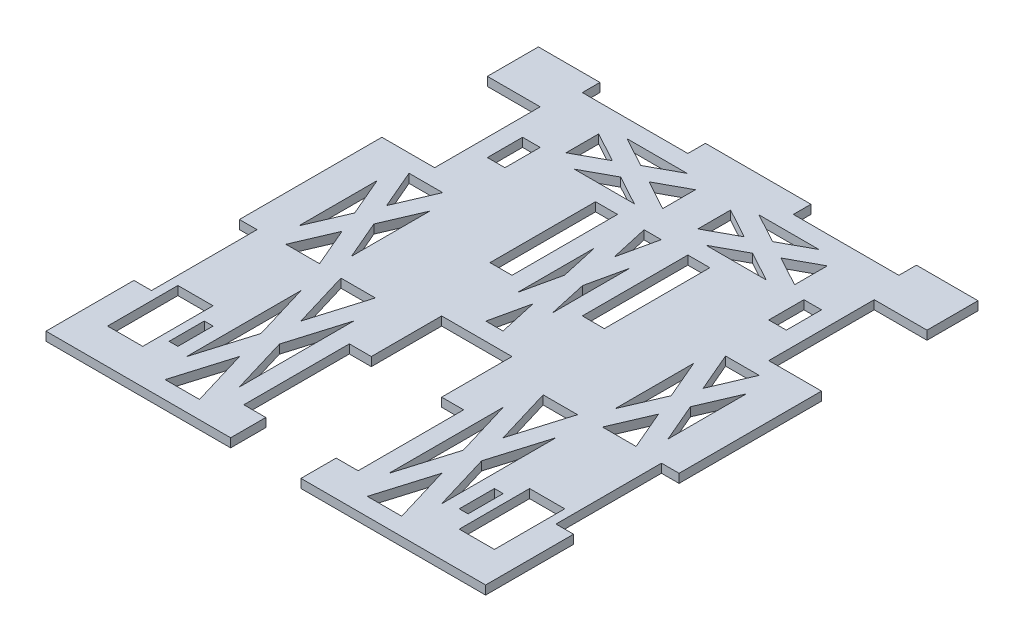
SolidWorks part; units mm, degrees
material "7050-T73510"
ref_plane "Front Plane" through (0, 0, 0) normal (0, 0, 1) x (1, 0, 0)
ref_plane "Top Plane" through (0, 0, 0) normal (0, 1, 0) x (1, 0, 0)
ref_plane "Right Plane" through (0, 0, 0) normal (1, 0, 0) x (0, 0, -1)
sketch "Sketch1" plane through (0, 0, 0) normal (0, 1, 0) x (1, 0, 0)
  line L1 (-158.75, -177.8) -> (158.75, -177.8)
  line L2 (-158.75, -177.8) -> (-158.75, 177.8)
  line L3 (-158.75, 177.8) -> (158.75, 177.8)
  line L4 (158.75, -177.8) -> (158.75, 177.8)
  line L5 (-158.75, -177.8) -> (158.75, 177.8) construction
  line L6 (-158.75, 177.8) -> (158.75, -177.8) construction
  point P0 (0, 0)
  dimension "D1" = 355.6
  dimension "D2" = 317.5
extrude "Boss-Extrude1" add sketch "Sketch1" along normal blind 6.35
sketch "Sketch2" plane through (0, 6.35, 0) normal (0, 1, 0) x (1, 0, 0)
  line L0 (-158.75, -177.8) -> (158.75, -177.8) construction
  line L1 (-25.4, -25.4) -> (25.4, -25.4)
  line L2 (-25.4, -25.4) -> (-25.4, -177.8)
  line L3 (-25.4, -177.8) -> (25.4, -177.8)
  line L4 (25.4, -25.4) -> (25.4, -177.8)
  line L5 (-25.4, -25.4) -> (25.4, -177.8) construction
  line L6 (-25.4, -177.8) -> (25.4, -25.4) construction
  point P0 (0, -101.6)
  dimension "D1" = 152.4
  dimension "D2" = 50.8
extrude "Cut-Extrude1" cut sketch "Sketch2" against normal through all
sketch "Sketch3" plane through (0, 6.35, 0) normal (0, 1, 0) x (1, 0, 0)
  line L0 (158.75, -177.8) -> (158.75, 177.8) construction
  line L5 (146.05, 140.97) -> (120.65, 140.97)
  line L11 (146.05, 140.97) -> (146.05, 64.77)
  line L13 (146.05, 64.77) -> (120.65, 64.77)
  line L15 (120.65, 140.97) -> (120.65, 64.77)
  line L16 (158.75, 177.8) -> (-158.75, 177.8) construction
  line L17 (107.95, 90.17) -> (95.25, 90.17)
  line L18 (107.95, 90.17) -> (107.95, 115.57)
  line L19 (107.95, 115.57) -> (95.25, 115.57)
  line L20 (95.25, 90.17) -> (95.25, 115.57)
  line L21 (0, -3.4925) -> (0, 3.4925) construction
  line L22 (-95.25, 90.17) -> (-95.25, 115.57)
  line L23 (-107.95, 115.57) -> (-95.25, 115.57)
  line L24 (-107.95, 90.17) -> (-107.95, 115.57)
  line L25 (-107.95, 90.17) -> (-95.25, 90.17)
  line L26 (-120.65, 140.97) -> (-120.65, 64.77)
  line L27 (-146.05, 64.77) -> (-120.65, 64.77)
  line L28 (-146.05, 140.97) -> (-146.05, 64.77)
  line L29 (-146.05, 140.97) -> (-120.65, 140.97)
  point P14 (107.95, 102.87)
  point P15 (120.65, 102.87)
  dimension "D1" = 25.4
  dimension "D2" = 12.7
  dimension "D3" = 12.7
  dimension "D4" = 12.7
  dimension "D5" = 25.4
  dimension "D6" = 76.2
  dimension "D7" = 36.83
extrude "Cut-Extrude2" cut sketch "Sketch3" against normal through all contours L5 L15 L13 L11 | L20 L17 L18 L19 | L29 L28 L27 L26 | L24 L25 L22 L23 | L26 L27 L28 L29 region at (133.35, 6.35, -102.87) region at (101.6, 6.35, -102.87) region at (-101.6, 6.35, -102.87) region at (-133.35, 6.35, -102.87)
sketch "Sketch4" plane through (0, 6.35, 0) normal (0, 1, 0) x (1, 0, 0)
  line L0 (-158.75, 177.8) -> (-158.75, -177.8) construction
  line L1 (-158.75, 140.97) -> (-146.05, 140.97)
  line L2 (-158.75, 140.97) -> (-158.75, 64.77)
  line L3 (-158.75, 64.77) -> (-146.05, 64.77)
  line L4 (-146.05, 140.97) -> (-146.05, 64.77)
  line L5 (0, -3.4925) -> (0, 3.4925) construction
  line L6 (-158.75, -114.3) -> (-146.05, -114.3)
  line L7 (-158.75, -114.3) -> (-158.75, -38.1)
  line L8 (-158.75, -38.1) -> (-146.05, -38.1)
  line L9 (-146.05, -114.3) -> (-146.05, -38.1)
  line L10 (158.75, 64.77) -> (146.05, 64.77)
  line L11 (146.05, 140.97) -> (146.05, 64.77)
  line L12 (158.75, 140.97) -> (146.05, 140.97)
  line L13 (158.75, 140.97) -> (158.75, 64.77)
  line L14 (158.75, -38.1) -> (146.05, -38.1)
  line L15 (146.05, -114.3) -> (146.05, -38.1)
  line L16 (158.75, -114.3) -> (146.05, -114.3)
  line L17 (158.75, -114.3) -> (158.75, -38.1)
  line L18 (158.75, 177.8) -> (-158.75, 177.8) construction
  line L19 (114.3, 165.1) -> (38.1, 165.1)
  line L20 (-114.3, 177.8) -> (-38.1, 177.8)
  line L21 (-114.3, 177.8) -> (-114.3, 165.1)
  line L22 (-114.3, 165.1) -> (-38.1, 165.1)
  line L23 (-38.1, 177.8) -> (-38.1, 165.1)
  line L24 (38.1, 177.8) -> (38.1, 165.1)
  line L25 (114.3, 177.8) -> (38.1, 177.8)
  line L26 (114.3, 177.8) -> (114.3, 165.1)
  line L27 (-25.4, -25.4) -> (-25.4, -177.8) construction
  line L28 (-25.4, -152.4) -> (-41.275, -152.4)
  line L29 (-25.4, -152.4) -> (-25.4, -76.2)
  line L30 (-25.4, -76.2) -> (-41.275, -76.2)
  line L31 (-41.275, -152.4) -> (-41.275, -76.2)
  line L32 (-158.75, -177.8) -> (-25.4, -177.8) construction
  line L33 (25.4, 101.6) -> (41.275, 101.6)
  line L34 (-25.4, 25.4) -> (-41.275, 25.4)
  line L35 (-25.4, 25.4) -> (-25.4, 101.6)
  line L36 (-25.4, 101.6) -> (-41.275, 101.6)
  line L37 (-41.275, 25.4) -> (-41.275, 101.6)
  line L38 (41.275, 25.4) -> (41.275, 101.6)
  line L39 (25.4, 25.4) -> (41.275, 25.4)
  line L40 (25.4, 25.4) -> (25.4, 101.6)
  line L41 (25.4, -76.2) -> (41.275, -76.2)
  line L42 (41.275, -152.4) -> (41.275, -76.2)
  line L43 (25.4, -152.4) -> (41.275, -152.4)
  line L44 (25.4, -152.4) -> (25.4, -76.2)
  dimension "D1" = 12.7
  dimension "D2" = 12.7
  dimension "D3" = 76.2
  dimension "D4" = 76.2
  dimension "D5" = 36.83
  dimension "D6" = 215.9
  dimension "D7" = 12.7
  dimension "D8" = 76.2
  dimension "D9" = 76.2
  dimension "D10" = 15.875
  dimension "D11" = 76.2
  dimension "D12" = 25.4
  dimension "D13" = 76.2
  dimension "D14" = 15.875
  dimension "D15" = 203.2
  dimension "D16" = 50.8
extrude "Cut-Extrude3" cut sketch "Sketch4" against normal through all
sketch "Sketch5" plane through (0, 6.35, 0) normal (0, 1, 0) x (1, 0, 0)
  line L0 (-158.75, -177.8) -> (-25.4, -177.8) construction
  line L1 (-92.075, -165.1) -> (-53.975, -165.1)
  line L2 (-92.075, -165.1) -> (-92.075, -38.1)
  line L3 (-92.075, -38.1) -> (-53.975, -38.1)
  line L4 (-53.975, -165.1) -> (-53.975, -38.1)
  line L5 (-92.075, -165.1) -> (-53.975, -38.1) construction
  line L6 (-92.075, -38.1) -> (-53.975, -165.1) construction
  line L7 (-133.35, -36.83) -> (-95.25, -36.83)
  line L8 (-133.35, -36.83) -> (-133.35, 52.07)
  line L9 (-133.35, 52.07) -> (-95.25, 52.07)
  line L10 (-95.25, -36.83) -> (-95.25, 52.07)
  line L11 (-133.35, -36.83) -> (-95.25, 52.07) construction
  line L12 (-133.35, 52.07) -> (-95.25, -36.83) construction
  line L13 (-82.55, 114.3) -> (-12.7, 114.3)
  line L14 (-82.55, 114.3) -> (-82.55, 152.4)
  line L15 (-82.55, 152.4) -> (-12.7, 152.4)
  line L16 (-12.7, 114.3) -> (-12.7, 152.4)
  line L17 (-82.55, 114.3) -> (-12.7, 152.4) construction
  line L18 (-82.55, 152.4) -> (-12.7, 114.3) construction
  line L23 (0, -3.4925) -> (0, 3.4925) construction
  line L24 (-12.7, -12.7) -> (12.7, -12.7)
  line L25 (-146.05, -114.3) -> (-146.05, -38.1) construction
  line L26 (-146.05, -38.1) -> (-158.75, -38.1) construction
  line L27 (-41.275, -76.2) -> (-41.275, -152.4) construction
  line L28 (-158.75, 64.77) -> (-158.75, -38.1) construction
  line L29 (-158.75, 64.77) -> (-120.65, 64.77) construction
  line L31 (-12.7, -12.7) -> (-12.7, 101.6)
  line L32 (-12.7, 101.6) -> (12.7, 101.6)
  line L33 (12.7, -12.7) -> (12.7, 101.6)
  line L34 (-12.7, -12.7) -> (12.7, 101.6) construction
  line L35 (-12.7, 101.6) -> (12.7, -12.7) construction
  line L36 (25.4, -25.4) -> (-25.4, -25.4) construction
  line L37 (-25.4, 25.4) -> (-25.4, 101.6) construction
  line L38 (-25.4, 101.6) -> (-41.275, 101.6) construction
  line L39 (-95.25, 90.17) -> (-95.25, 115.57) construction
  line L40 (-114.3, 165.1) -> (-38.1, 165.1) construction
  line L41 (-98.1572, -39.9247) -> (-60.0572, -166.9247)
  line L42 (-85.9928, -166.9247) -> (-47.8928, -39.9247)
  line L43 (-139.1866, 49.5686) -> (-101.0866, -39.3314)
  line L44 (-127.5134, -39.3314) -> (-89.4134, 49.5686)
  line L45 (-18.8988, 100.2225) -> (6.5012, -14.0775)
  line L46 (-6.5012, -14.0775) -> (18.8988, 100.2225)
  line L47 (-85.5907, 146.8254) -> (-15.7407, 108.7254)
  line L48 (-79.5093, 108.7254) -> (-9.6593, 146.8254)
  line L49 (-85.9928, -36.2753) -> (-47.8928, -163.2753)
  line L50 (-98.1572, -163.2753) -> (-60.0572, -36.2753)
  line L51 (-127.5134, 54.5714) -> (-89.4134, -34.3286)
  line L52 (-139.1866, -34.3286) -> (-101.0866, 54.5714)
  line L53 (-6.5012, 102.9775) -> (18.8988, -11.3225)
  line L54 (-18.8988, -11.3225) -> (6.5012, 102.9775)
  line L55 (-79.5093, 157.9746) -> (-9.6593, 119.8746)
  line L56 (-85.5907, 119.8746) -> (-15.7407, 157.9746)
  line L57 (-139.7, -101.6) -> (-114.3, -101.6)
  line L58 (-139.7, -101.6) -> (-139.7, -152.4)
  line L59 (-139.7, -152.4) -> (-114.3, -152.4)
  line L60 (-114.3, -101.6) -> (-114.3, -152.4)
  line L63 (-107.95, -139.7) -> (-101.6, -139.7)
  line L64 (-107.95, -139.7) -> (-107.95, -114.3)
  line L65 (-107.95, -114.3) -> (-101.6, -114.3)
  line L66 (-101.6, -139.7) -> (-101.6, -114.3)
  line L67 (-107.95, -139.7) -> (-101.6, -114.3) construction
  line L68 (-107.95, -114.3) -> (-101.6, -139.7) construction
  point P0 (-73.025, -101.6)
  point P5 (-114.3, 7.62)
  point P10 (-47.625, 133.35)
  point P15 (0, 44.45)
  point P27 (-152.4, -38.1)
  point P34 (-104.775, -127)
  point P45 (-33.3375, 101.6)
  point P87 (-114.3, -127)
  dimension "D1" = 12.7
  dimension "D2" = 38.1
  dimension "D3" = 0
  dimension "D4" = 12.7
  dimension "D5" = 88.9
  dimension "D6" = 25.4
  dimension "D7" = 12.7
  dimension "D8" = 38.1
  dimension "D9" = 12.7
  dimension "D10" = 12.7
  dimension "D11" = 12.7
  dimension "D12" = 12.7
  dimension "D13" = 12.7
  dimension "D14" = 12.7
  dimension "D17" = 25.4
  dimension "D18" = 50.8
  dimension "D19" = 12.7
  dimension "D20" = 6.35
  dimension "D21" = 6.35
  dimension "D22" = 38.1
  dimension "D23" = 25.4
  dimension "D15" = 6.35
  dimension "D16" = 6.35
extrude "Cut-Extrude4" cut sketch "Sketch5" against normal through all contours L42 L1 L41 | L2 L50 L41 | L49 L50 L3 | L42 L49 L4 | L44 L7 L43 | L8 L52 L43 | L51 L52 L9 | L44 L51 L10 | L46 L53 L33 | L53 L54 L32 | L31 L54 L45 | L46 L24 L45 | L48 L13 L47 | L48 L55 L16 | L55 L56 L15 | L14 L56 L47 | L60 L57 L58 L59 | L63 L66 L65 L64 region at (-73.025, 6.35, 151.2995) region at (-87.9349, 6.35, 101.6) region at (-58.1151, 6.35, 101.6) region at (-73.025, 6.35, 51.9005) region at (-114.3, 6.35, 27.3867) region at (-129.3029, 6.35, -7.62) region at (-99.2971, 6.35, -7.62) region at (-114.3, 6.35, -42.6267) region at (-47.625, 6.35, -118.2389) region at (-75.3286, 6.35, -133.35) region at (-19.9214, 6.35, -133.35) region at (-47.625, 6.35, -148.4611) region at (0, 6.35, 3.4074) region at (-10.635, 6.35, -44.45) region at (10.635, 6.35, -44.45) region at (0, 6.35, -92.3074) region at (-127, 6.35, 127) region at (-104.775, 6.35, 127)
mirror "Mirror1" about plane through (0, 0, 0) normal (1, 0, 0) of "Cut-Extrude4"
